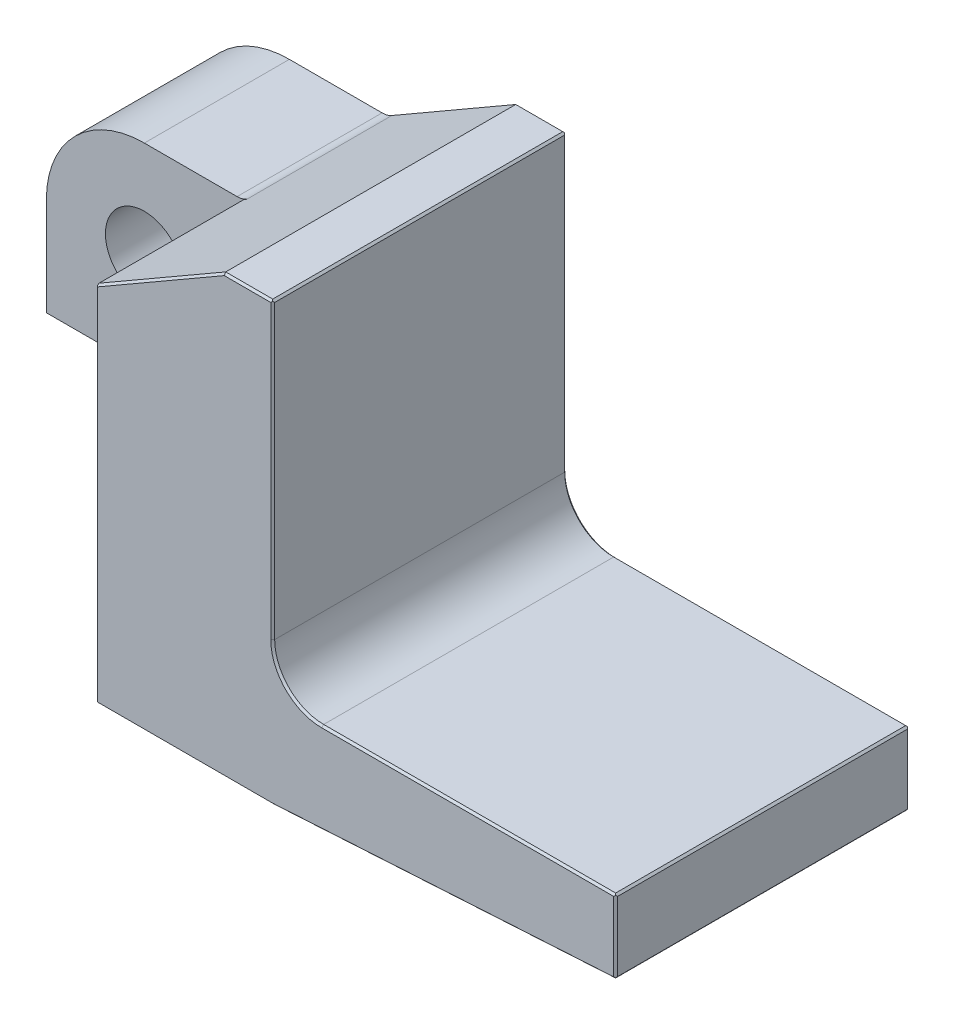
SolidWorks part; units mm, degrees
material "7075-T6 (SN)"
ref_plane "Front Plane" through (0, 0, 0) normal (0, 0, 1) x (1, 0, 0)
ref_plane "Top Plane" through (0, 0, 0) normal (0, 1, 0) x (1, 0, 0)
ref_plane "Right Plane" through (0, 0, 0) normal (1, 0, 0) x (0, 0, -1)
sketch "Sketch1" plane through (0, 0, 0) normal (0, 0, 1) x (1, 0, 0)
  line L0 (0, 0) -> (44.45, 0)
  line L1 (44.45, 0) -> (44.45, -9.525)
  line L2 (-22.9902, 9.4453) -> (-48.3902, 9.4453)
  line L3 (-48.3902, 9.4453) -> (-48.3902, 22.1453)
  line L7 (0, 44.45) -> (0, 0)
  line L8 (-22.9902, 9.4453) -> (-22.9902, -12.1447)
  line L13 (-35.6902, 34.8453) -> (-22.9902, 34.8453)
  line L15 (-22.9902, 34.8453) -> (-6.35, 44.45)
  line L16 (-6.35, 44.45) -> (0, 44.45)
  line L17 (-22.9902, -12.1447) -> (0, -12.1447)
  line L18 (0, -12.1447) -> (44.45, -9.525)
  arc A0 (-35.6902, 34.8453) -> (-48.3902, 22.1453) centre (-35.6902, 22.1453) ccw
  dimension "D5" = 12.7
  dimension "D1" = 44.45
  dimension "D2" = 25.4
  dimension "D3" = 9.525
  dimension "D4" = 35.6902
  dimension "D6" = 9.4453
  dimension "D7" = 25.4
  dimension "D8" = 12.7
  dimension "D9" = 21.59
  dimension "D11" = 44.45
  dimension "D12" = 6.35
extrude "Boss-Extrude1" add sketch "Sketch1" along normal blind 38.1
fillet "Fillet2" radius 6.35 1 edges at (0, 0, 19.05)
sketch "Sketch3" plane through (0, 0, 38.1) normal (0, 0, 1) x (1, 0, 0)
  line L0 (-48.3902, 9.4453) -> (-22.9902, 9.4453) construction
  line L1 (-48.3902, 22.1453) -> (-48.3902, 9.4453) construction
  line L2 (-22.9902, 34.8453) -> (-35.6902, 34.8453) construction
  line L3 (-48.3902, 9.4453) -> (-22.9902, 9.4453)
  line L4 (-48.3902, 22.1453) -> (-48.3902, 9.4453)
  line L5 (-22.9902, 34.8453) -> (-35.6902, 34.8453)
  line L6 (-22.9902, 34.8453) -> (-22.9902, 9.4453)
  arc A0 (-35.6902, 34.8453) -> (-48.3902, 22.1453) centre (-35.6902, 22.1453) ccw construction
  arc A1 (-35.6902, 34.8453) -> (-48.3902, 22.1453) centre (-35.6902, 22.1453) ccw
  point P6 (-29.5402, -3.715)
extrude "Cut-Extrude1" cut sketch "Sketch3" against normal blind 19.05
fillet "Fillet3" radius 2.54 1 edges at (-22.9902, 34.8453, 9.525)
sketch "Sketch4" plane through (0, 0, 0) normal (0, 0, -1) x (-1, 0, 0)
  arc A0 (48.3902, 22.1453) -> (35.6902, 34.8453) centre (35.6902, 22.1453) ccw construction
  point P0 (35.6902, 22.1453)
hole_wizard "CBORE for 3/8 Binding Head Machine Screw1" positions "Sketch4" profile "Sketch5" counterbore size "3/8" standard "ANSI Inch" end condition through all
sketch "Sketch5" plane through (-35.6902, 22.1453, 0) normal (1, 0, 0) x (0, 1, 0)
  line L0 (0, 0) -> (0, 38.1)
  line L1 (0, 38.1) -> (5.0419, 38.1)
  line L3 (5.0419, 38.1) -> (5.0419, 6.4262)
  line L4 (5.0419, 6.4262) -> (10.414, 6.4262)
  line L5 (10.414, 6.4262) -> (10.414, 0)
  line L7 (10.414, 0) -> (0, 0)
  line L11 (0, -6.35) -> (0, 107.95) construction
  dimension "Thru Hole Dia." = 10.0838
  dimension "Thru Hole Depth" = 38.1
  dimension "C'Bore Dia." = 20.828
  dimension "C'Bore Depth" = 6.4262
chamfer "Chamfer3" distance 0.254 angle 45 8 edges at (44.45, 0, 19.05) (25.4, 0, 38.1) (25.4, 0, 0) (1.8599, 1.8599, 0) (1.8599, 1.8599, 38.1) (0, 25.4, 0) (0, 44.45, 19.05) (0, 25.4, 38.1)
chamfer "Chamfer5" distance 0.254 angle 45 11 edges at (44.45, -4.8895, 38.1) (44.45, -9.525, 19.05) (44.45, -4.8895, 0) (-48.3902, 15.7953, 0) (-44.6705, 31.1256, 0) (-29.6804, 34.8453, 0) (-23.0134, 34.9319, 0) (-14.3754, 39.8177, 0) (-3.302, 44.45, 0) (-14.6701, 39.6477, 38.1) (-3.302, 44.45, 38.1)
chamfer "Chamfer6" distance 0.254 angle 45 8 edges at (-22.9902, 34.8453, 28.448) (-22.9902, -1.3497, 0) (22.098, -10.8423, 0) (-11.4951, -12.1447, 0) (-22.9902, -12.1447, 19.05) (-22.9902, 11.2037, 38.1) (-11.4951, -12.1447, 38.1) (22.098, -10.8423, 38.1)
